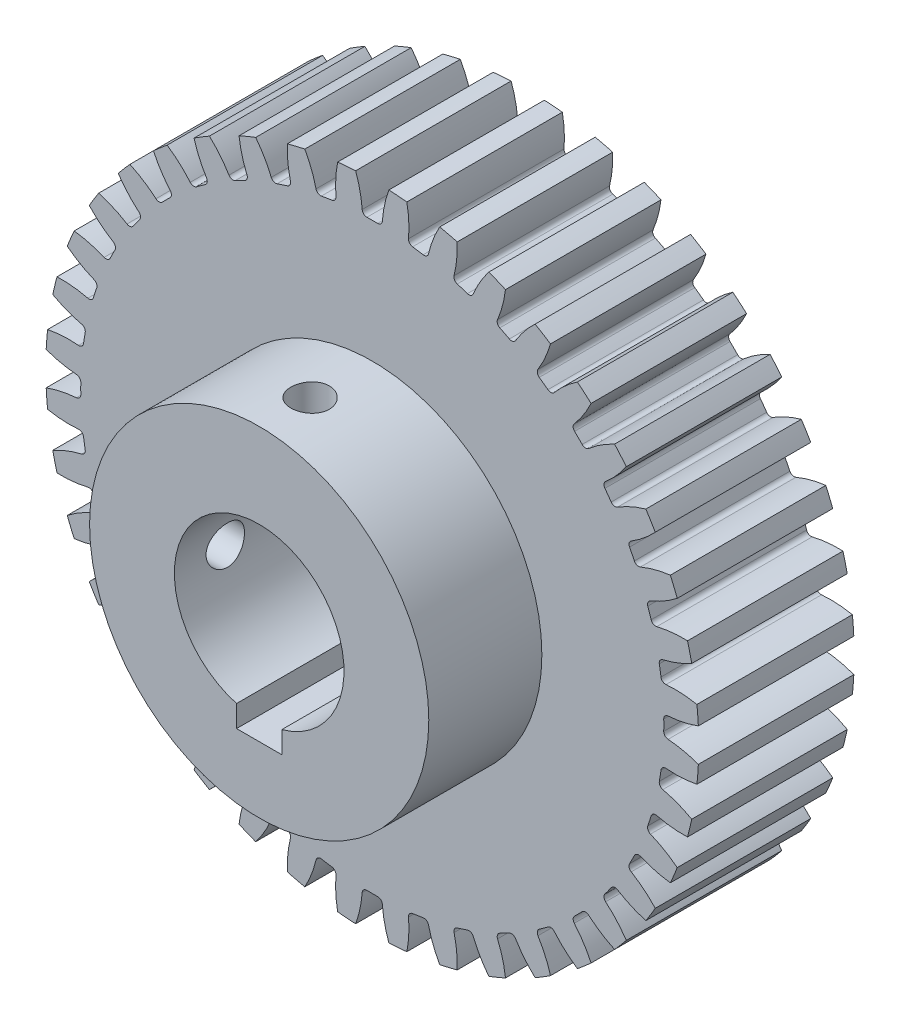
SolidWorks part; units mm, degrees
ref_plane "Ön Düzlem" through (0, 0, 0) normal (0, 0, 1) x (1, 0, 0)
ref_plane "Üst Düzlem" through (0, 0, 0) normal (0, 1, 0) x (1, 0, 0)
ref_plane "Sağ Düzlem" through (0, 0, 0) normal (1, 0, 0) x (0, 0, -1)
sketch "Sketch1" plane through (0, 0, 0) normal (0, 0, 1) x (1, 0, 0)
  circle A0 centre (0, 0) radius 57.75
  dimension "D1" = 115.5
extrude "Boss-Extrude1" add sketch "Sketch1" along normal mid plane 27.5
sketch "Sketch2" plane through (0, 0, 13.75) normal (0, 0, 1) x (1, 0, 0)
  line L0 (0, 0) -> (0, 57.75) construction
  line L1 (0, 0) -> (-2.5153, 64.0195) construction
  line L2 (-1.7426, 51.533) -> (0, 0) construction
  line L3 (-3.1643, 58.2578) -> (11.158, 22.6959) construction
  circle A0 centre (0, 0) radius 57.75 construction
  circle A1 centre (0, 0) radius 55 construction
  arc A2 (1.7426, 51.533) -> (-1.7426, 51.533) centre (0, 0) ccw
  arc A3 (-3.1643, 58.2578) -> (-1.7426, 51.533) centre (-21.5224, 50.8642) cw
  arc A4 (3.1643, 58.2578) -> (1.7426, 51.533) centre (21.5224, 50.8642) ccw
  arc A5 (-3.1643, 58.2578) -> (3.1643, 58.2578) centre (0, 0) cw
  point P12 (-2.1593, 54.9576)
  dimension "D2" = 103.125
  dimension "D3" = 110
  dimension "D1" = 2.25
  dimension "D4" = 20
extrude "Cut-Extrude1" cut sketch "Sketch2" against normal blind 27.5
fillet "Fillet1" radius 0.825 2 edges at (1.7426, 51.533, 0) (-1.7426, 51.533, 0)
pattern_circular "CirPattern1" count 40 over 360 about axis through (0, 0, 13.75) along (0, 0, 1) of "Fillet1", "Cut-Extrude1"
sketch "Sketch3" plane through (0, 0, 13.75) normal (0, 0, 1) x (1, 0, 0)
  circle A0 centre (0, 0) radius 30
  dimension "D1" = 60
extrude "Boss-Extrude2" add sketch "Sketch3" along normal blind 20
sketch "Sketch4" plane through (0, 0, 33.75) normal (0, 0, 1) x (1, 0, 0)
  circle A0 centre (0, 0) radius 15
  dimension "D1" = 30
extrude "Cut-Extrude2" cut sketch "Sketch4" against normal through all
ref_plane "Plane1" through (0, 30, 0) normal (0, 1, 0) x (1, 0, 0)
hole_wizard "M8 Tapped Hole1" positions "Sketch5" profile "Sketch6" tap size "M8" standard "ISO"
sketch "Sketch5" plane through (0, 30, 0) normal (0, 1, 0) x (1, 0, 0)
  line L0 (-30, -33.75) -> (30, -33.75) construction
  point P0 (0, -24.75)
  point P5 (0, 0)
  dimension "D1" = 9
sketch "Sketch6" plane through (0, 30, 24.75) normal (1, 0, 0) x (0, 0, 1)
  line L0 (0, 0) -> (0, 24.2929)
  line L1 (0, 24.2929) -> (3.4, 22.25)
  line L2 (3.4, 22.25) -> (3.4, 0)
  line L5 (3.4, 0) -> (0, 0)
  line L10 (0, 24.2929) -> (-3.4, 22.25) construction
  line L11 (0, -6.35) -> (0, 107.95) construction
  dimension "Tap Drill Dia." = 6.8
  dimension "Tap Drill Depth" = 22.25
  dimension "Drill Angle" = 118
cosmetic thread "Hole Thread1" parameters "D1"=16, "D2"=8
pattern_circular "CirPattern2" count 2 over 90 about axis through (0, 0, 33.75) along (0, 0, 1) of "M8 Tapped Hole1"
cosmetic thread "Hole Thread2" parameters "D1"=16, "D2"=8
sketch "Sketch7" plane through (0, 0, 0) normal (0, 1, 0) x (1, 0, 0)
  line L0 (-30, -33.75) -> (30, -33.75) construction
  line L1 (-4, -33.75) -> (4, -33.75)
  line L2 (-4, -33.75) -> (-4, 13.75)
  line L3 (-4, 13.75) -> (4, 13.75)
  line L4 (4, -33.75) -> (4, 13.75)
  line L5 (15.0263, 13.75) -> (11.9264, 13.75) construction
  point P8 (0, -33.75)
  dimension "D1" = 8
extrude "Cut-Extrude3" cut sketch "Sketch7" against normal blind 18.3
equation "\"m\"= 2.75'modül"
equation "\"z\"= 40'diş sayısı"
equation "\"Pa\"= 20'profil açısı"
equation "\"Do\"= \"m\" * \"z\"'bölüm dairesi çapı"
equation "\"Da\"= \"Do\" + ( 2 * \"m\" )'diş üstü çapı"
equation "\"Df\"= \"Do\" - ( \"m\" * 2.5 )'diş dibi çapı"
equation "\"a\"= 360 / ( \"z\" * 4 )'tasarım açısı"
equation "\"r\"= \"m\" * 0.3'diş dibi radyusu"
equation "\"b\"= \"m\" * 10'diş genişliği"
equation "\"D1@Sketch1\"=\"Da\""
equation "\"D1@Boss-Extrude1\"=\"b\""
equation "\"D1@Sketch2\"=\"a\""
equation "\"D2@Sketch2\"=\"Df\""
equation "\"D3@Sketch2\"=\"Do\""
equation "\"D1@Fillet1\"=\"r\""
equation "\"D1@CirPattern1\"=\"z\""
